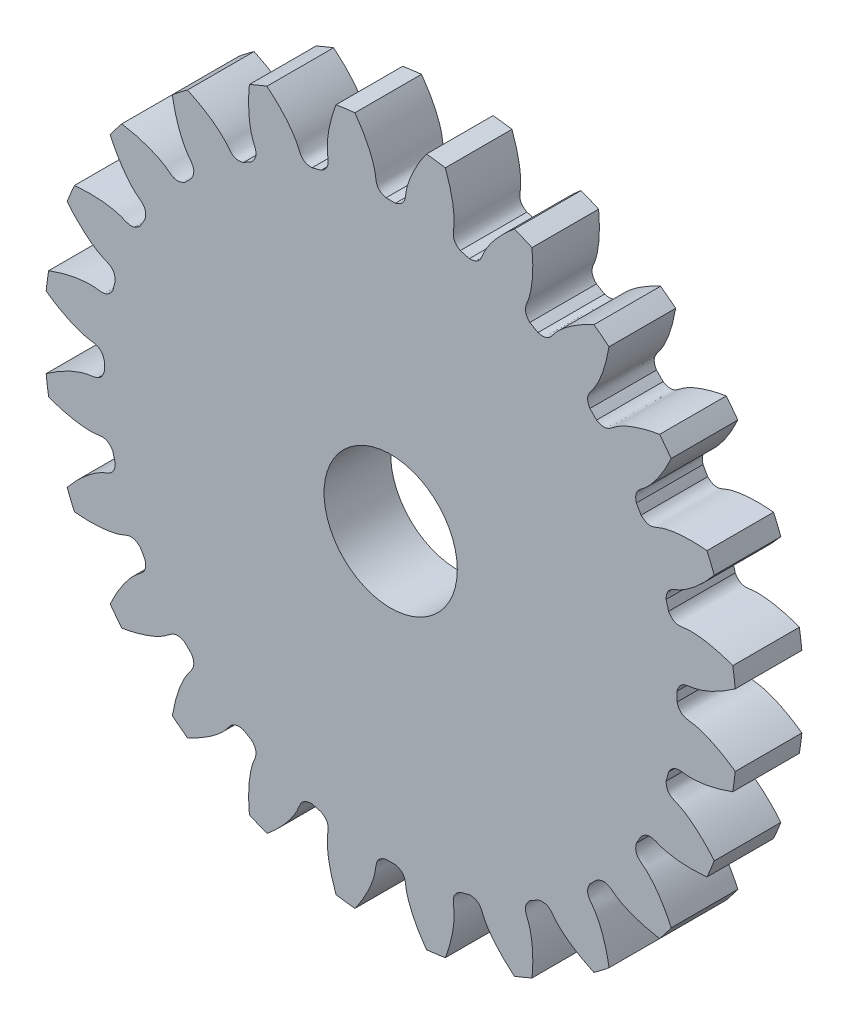
SolidWorks part; units mm, degrees
material "Thornel Mat VMA"
ref_plane "前视基准面" through (0, 0, 0) normal (0, 0, 1) x (1, 0, 0)
ref_plane "上视基准面" through (0, 0, 0) normal (0, 1, 0) x (1, 0, 0)
ref_plane "右视基准面" through (0, 0, 0) normal (1, 0, 0) x (0, 0, -1)
sketch "草图1" plane through (0, 0, 0) normal (0, 0, 1) x (1, 0, 0)
  circle A0 centre (0, 0) radius 26
extrude "凸台-拉伸1" add sketch "草图1" along normal mid plane 5
ref_axis "基准轴1" through (0, 0, -0.25) along (0, 0, 1)
sketch "草图2" plane through (0, 0, 0) normal (0, 0, 1) x (1, 0, 0)
  line L0 (0, 0) -> (0, 26) construction
  circle A0 centre (0, 0) radius 26 construction
  arc A1 (0.3537, 21.4971) -> (-0.3537, 21.4971) centre (0, 0) ccw
  arc A2 (6.2312, 29.3882) -> (-6.2312, 29.3882) centre (0, 0) ccw
  spline S0 degree 3 poles (0.3537, 21.4971) (1.1358, 21.7137) (1.0781, 22.2314) (1.1726, 22.7454) (1.1861, 22.8117) (1.2029, 22.8865) (1.2234, 22.9697) (1.2478, 23.0612) (1.2766, 23.1609) (1.31, 23.2686) (1.3484, 23.3842) (1.3922, 23.5075) (1.4416, 23.6383) (1.4969, 23.7765) (1.5585, 23.9218) (1.6267, 24.0742) (1.7018, 24.2333) (1.784, 24.3989) (1.8737, 24.5709) (1.9712, 24.7489) (2.0767, 24.9328) (2.1904, 25.1223) (2.3128, 25.3171) (2.444, 25.517) (2.5842, 25.7216) (2.7338, 25.9308) (2.8929, 26.1441) (3.0617, 26.3614) (3.2406, 26.5822) (3.4296, 26.8063) (3.6291, 27.0334) (3.8391, 27.2631) (4.0599, 27.495) (4.2917, 27.729) (4.5345, 27.9645) (4.7886, 28.2013) (5.0542, 28.4389) (5.3312, 28.6771) (5.7208, 28.9987) (6.0238, 29.2338) (6.2312, 29.3882) knots 0 0 0 0 0.143961 0.149818 0.156577 0.164236 0.172796 0.182258 0.19262 0.203884 0.216049 0.229115 0.243082 0.25795 0.273719 0.290389 0.30796 0.326433 0.345806 0.366081 0.387257 0.409333 0.432311 0.45619 0.48097 0.506651 0.533234 0.560717 0.589101 0.618387 0.648574 0.679661 0.71165 0.74454 0.778331 0.813023 0.848616 0.885111 0.922506 1 1 1 1
  spline S1 degree 3 poles (-0.3537, 21.4971) (-1.1358, 21.7137) (-1.0781, 22.2314) (-1.1726, 22.7454) (-1.1861, 22.8117) (-1.2029, 22.8865) (-1.2234, 22.9697) (-1.2478, 23.0612) (-1.2766, 23.1609) (-1.31, 23.2686) (-1.3484, 23.3842) (-1.3922, 23.5075) (-1.4416, 23.6383) (-1.4969, 23.7765) (-1.5585, 23.9218) (-1.6267, 24.0742) (-1.7018, 24.2333) (-1.784, 24.3989) (-1.8737, 24.5709) (-1.9712, 24.7489) (-2.0767, 24.9328) (-2.1904, 25.1223) (-2.3128, 25.3171) (-2.444, 25.517) (-2.5842, 25.7216) (-2.7338, 25.9308) (-2.8929, 26.1441) (-3.0617, 26.3614) (-3.2406, 26.5822) (-3.4296, 26.8063) (-3.6291, 27.0334) (-3.8391, 27.2631) (-4.0599, 27.495) (-4.2917, 27.729) (-4.5345, 27.9645) (-4.7886, 28.2013) (-5.0542, 28.4389) (-5.3312, 28.6771) (-5.7208, 28.9987) (-6.0238, 29.2338) (-6.2312, 29.3882) knots 0 0 0 0 0.143961 0.149818 0.156577 0.164236 0.172796 0.182258 0.19262 0.203884 0.216049 0.229115 0.243082 0.25795 0.273719 0.290389 0.30796 0.326433 0.345806 0.366081 0.387257 0.409333 0.432311 0.45619 0.48097 0.506651 0.533234 0.560717 0.589101 0.618387 0.648574 0.679661 0.71165 0.74454 0.778331 0.813023 0.848616 0.885111 0.922506 1 1 1 1
extrude "切除-拉伸1" cut sketch "草图2" along normal through all both and the other way through all
pattern_circular "阵列(圆周)1" count 24 every 15 about axis through (0, 0, -0.25) along (0, 0, 1) of "切除-拉伸1"
sketch "草图3" plane through (0, 0, 0) normal (0, 0, 1) x (1, 0, 0)
  circle A0 centre (0, 0) radius 24 construction
  dimension "Dn" = 48
sketch "草图4" plane through (0, 0, 2.5) normal (0, 0, 1) x (1, 0, 0)
  circle A0 centre (0, 0) radius 5
  dimension "D1" = 10
extrude "切除-拉伸2" cut sketch "草图4" against normal blind 10
